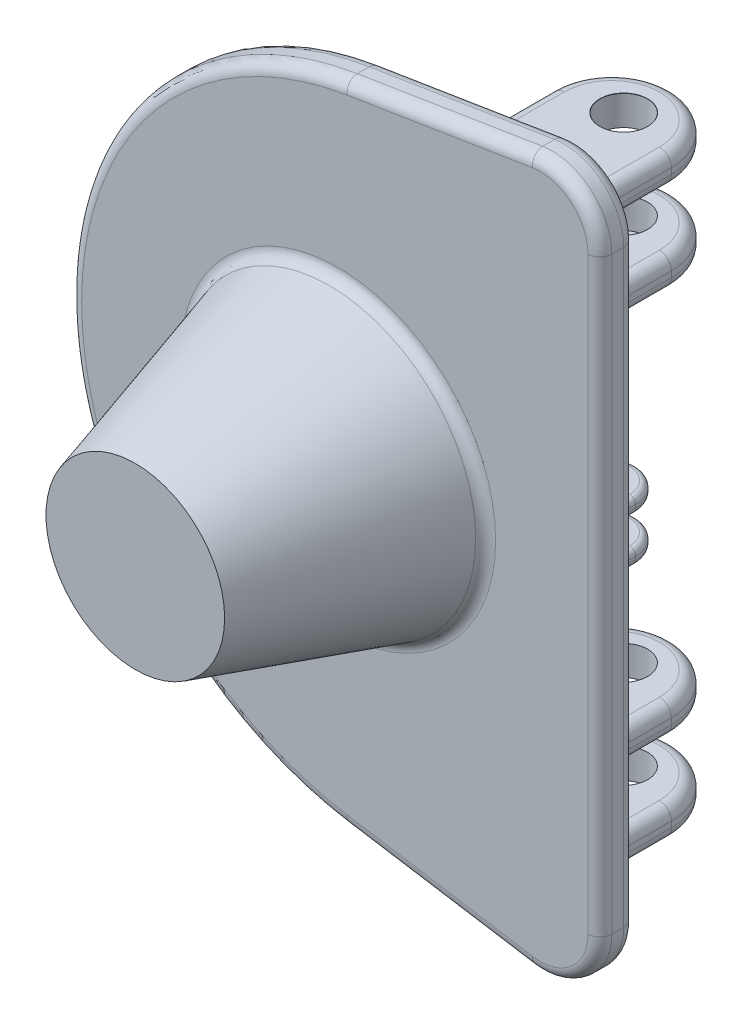
SolidWorks part; units mm, degrees
material "Maraging"
ref_plane "Front Plane" through (0, 0, 0) normal (0, 0, 1) x (1, 0, 0)
ref_plane "Top Plane" through (0, 0, 0) normal (0, 1, 0) x (1, 0, 0)
ref_plane "Right Plane" through (0, 0, 0) normal (1, 0, 0) x (0, 0, -1)
sketch "Sketch1" plane through (0, 0, 0) normal (0, 0, 1) x (1, 0, 0)
  line L0 (34, 49.4368) -> (34, -49.4368)
  line L3 (-8.7311, 54.3026) -> (22.4125, 59.31)
  line L4 (22.4125, -59.31) -> (-8.7311, -54.3026)
  circle A0 centre (0, 0) radius 60 construction
  arc A4 (-8.7311, 54.3026) -> (-8.7311, -54.3026) centre (0, 0) ccw
  arc A5 (34, -49.4368) -> (22.4125, -59.31) centre (24, -49.4368) cw
  arc A6 (34, 49.4368) -> (22.4125, 59.31) centre (24, 49.4368) ccw
  point P5 (34, -61.1731)
  point P13 (34, 61.1731)
  dimension "D1" = 120
  dimension "D2" = 55
  dimension "D3" = 34
  dimension "D4" = 10
extrude "Boss-Extrude1" add sketch "Sketch1" along normal blind 6
ref_plane "Plane1" through (-45, 0, 0) normal (1, 0, 0) x (0, 0, -1)
ref_plane "Plane2" through (5, 0, 0) normal (1, 0, 0) x (0, 0, -1)
sketch "Sketch9" plane through (-45, 0, 0) normal (1, 0, 0) x (0, 0, -1)
  line L0 (0, -10) -> (0, 10)
  line L3 (4, 3) -> (4, -3)
  line L4 (6, -5) -> (25, -5)
  line L5 (25, -10) -> (0, -10)
  line L6 (14.8178, 0) -> (-10.7829, 0) construction
  line L7 (25, 10) -> (0, 10)
  line L8 (6, 5) -> (25, 5)
  line L9 (25, -5) -> (25, -10)
  line L10 (25, 5) -> (25, 10)
  arc A2 (6, 5) -> (4, 3) centre (6, 3) ccw
  arc A3 (4, -3) -> (6, -5) centre (6, -3) ccw
  point P7 (12.5, -10)
  point P14 (4, 0)
  point P15 (0, 0)
  point P20 (4, 5)
  point P23 (4, -5)
  dimension "D5" = 2
  dimension "D2" = 4
  dimension "D4" = 5
  dimension "D1" = 25
  dimension "D3" = 5
extrude "Boss-Extrude3" add sketch "Sketch9" along normal blind 20
hole_wizard "Ø8.0mm Dowel Hole2" positions "3DSketch3" profile "Sketch10" hole size "Ø8.0" standard "ISO"
sketch3d "3DSketch3"
  line L0 (-25, 10, 0) -> (-45, 10, 0) construction
  point P0 (-35, 10, -17)
  point P6 (-35, 10, 0)
  dimension "D1" = 17
sketch "Sketch10" plane through (-35, 10, -17) normal (1, 0, 0) x (0, 0, 1)
  line L0 (0, 0) -> (0, 26.9034)
  line L1 (0, 26.9034) -> (4, 24.5)
  line L2 (4, 24.5) -> (4, 0.025)
  line L3 (4, 0.025) -> (4.025, 0)
  line L5 (4.025, 0) -> (0, 0)
  line L6 (-4, 0.025) -> (-4.025, 0) construction
  line L10 (0, 26.9034) -> (-4, 24.5) construction
  line L11 (0, -6.35) -> (0, 107.95) construction
  dimension "Hole Dia." = 8
  dimension "Hole Depth" = 24.5
  dimension "Near C'Sink Dia." = 8.05
  dimension "Near C'Sink Angle" = 90
  dimension "Drill Angle" = 118
sketch "Sketch11" plane through (0, 10, 0) normal (0, 1, 0) x (1, 0, 0)
  line L2 (-45, -18.15) -> (-45, 18.15) construction
  line L3 (-45, 15) -> (-45, 25)
  line L4 (-45, 25) -> (-25, 25)
  line L5 (-25, 25) -> (-25, 15)
  line L6 (-25, 25) -> (-25, 0) construction
  line L8 (-25, 25) -> (-45, 25) construction
  arc A0 (-45, 15) -> (-25, 15) centre (-35, 15) cw
  point P7 (-35, 25)
  line M6 (-45, 25) -> (-45, 0)
  line M8 (-25, 0) -> (-25, 25)
  line M9 (-25, 25) -> (-45, 25)
extrude "Cut-Extrude3" cut sketch "Sketch11" against normal blind 30 contours A0 L4 M6 | A0 M9 M8 region at (-27.2337, 10, -22.7663) region at (-42.7663, 10, -22.7663)
sketch "Sketch14" plane through (5, 0, 0) normal (1, 0, 0) x (0, 0, -1)
  line L0 (0, 40) -> (0, 30)
  line L2 (0, 30) -> (25, 30)
  line L3 (25, 30) -> (25, 35)
  line L4 (25, 35) -> (6, 35)
  line L5 (4, 37) -> (4, 43)
  line L6 (32.8816, 40) -> (-15.0482, 40) construction
  line L7 (25, 45) -> (6, 45)
  line L8 (25, 50) -> (25, 45)
  line L9 (0, 50) -> (25, 50)
  line L10 (0, 40) -> (0, 50)
  line L11 (0, -49.4368) -> (0, 49.4368) construction
  arc A0 (6, 35) -> (4, 37) centre (6, 37) cw
  arc A1 (6, 45) -> (4, 43) centre (6, 43) ccw
  point P14 (0, 35)
  point P17 (4, 40)
  point P22 (4, 35)
  point P25 (4, 45)
  dimension "D1" = 25
  dimension "D6" = 2
  dimension "D2" = 5
  dimension "D3" = 5
  dimension "D4" = 4
  dimension "D5" = 40
extrude "Boss-Extrude5" add sketch "Sketch14" along normal blind 20 contours L4 A0 L5 A1 L7 L8 L9 L10 L0 L2 L3
hole_wizard "Ø8.0mm Dowel Hole3" positions "3DSketch5" profile "Sketch17" hole size "Ø8.0" standard "ISO"
sketch3d "3DSketch5"
  line L0 (25, 50, 0) -> (5, 50, 0) construction
  point P0 (15, 50, -17)
  point P8 (15, 50, 0)
  dimension "D1" = 17
sketch "Sketch17" plane through (15, 50, -17) normal (1, 0, 0) x (0, 0, 1)
  line L0 (0, 0) -> (0, 26.9034)
  line L1 (0, 26.9034) -> (4, 24.5)
  line L2 (4, 24.5) -> (4, 0.025)
  line L3 (4, 0.025) -> (4.025, 0)
  line L5 (4.025, 0) -> (0, 0)
  line L6 (-4, 0.025) -> (-4.025, 0) construction
  line L10 (0, 26.9034) -> (-4, 24.5) construction
  line L11 (0, -6.35) -> (0, 107.95) construction
  dimension "Hole Dia." = 8
  dimension "Hole Depth" = 24.5
  dimension "Near C'Sink Dia." = 8.05
  dimension "Near C'Sink Angle" = 90
  dimension "Drill Angle" = 118
mirror "Mirror1" about plane through (0, 0, 0) normal (0, 1, 0) of "Ø8.0mm Dowel Hole3", "Boss-Extrude5"
sketch "Sketch19" plane through (0, 50, 0) normal (0, 1, 0) x (1, 0, 0)
  line L0 (5, 15) -> (5, 25)
  line L1 (5, 0) -> (5, 25) construction
  line L2 (5, 25) -> (25, 25)
  line L3 (25, 25) -> (25, 15)
  line L4 (25, 0) -> (25, 25) construction
  arc A0 (25, 15) -> (5, 15) centre (15, 15) ccw
  point P11 (15, 25)
  line M3 (5, 25) -> (5, 0)
  line M5 (25, 0) -> (25, 25)
  line M6 (25, 25) -> (5, 25)
extrude "Cut-Extrude4" cut sketch "Sketch19" against normal through all contours A0 L2 M3 | A0 M5 M6 region at (22.7663, 50, -22.7663) region at (7.2337, 50, -22.7663)
sketch "Sketch22" plane through (0, 0, 0) normal (1, 0, 0) x (0, 0, -1)
  line L15 (0, 27) -> (34, 27)
  line L17 (34, 27) -> (34, 24.5)
  line L18 (34, 24.5) -> (6, 24.5)
  line L19 (4, 22.5) -> (4, 21.5)
  line L20 (6, 19.5) -> (34, 19.5)
  line L21 (34, 19.5) -> (34, 17)
  line L22 (34, 17) -> (0, 17)
  line L23 (0, 17) -> (0, 27)
  line L24 (0, -49.4368) -> (0, 49.4368) construction
  arc A0 (4, 21.5) -> (6, 19.5) centre (6, 21.5) ccw
  arc A1 (6, 24.5) -> (4, 22.5) centre (6, 22.5) ccw
  point P4 (0, 22)
  point P13 (4, 19.5)
  point P16 (4, 24.5)
  dimension "D6" = 2
  dimension "D2" = 5
  dimension "D1" = 34
  dimension "D3" = 4
  dimension "D5" = 22
  dimension "D4" = 2.5
extrude "Boss-Extrude6" add sketch "Sketch22" against normal mid plane 10
hole_wizard "Ø5.0mm Dowel Hole1" positions "3DSketch6" profile "Sketch23" hole size "Ø5.0" standard "ISO"
sketch3d "3DSketch6"
  line L0 (-5, 17, 0) -> (5, 17, 0) construction
  point P0 (0, 17, -29)
  point P5 (0, 17, 0)
  dimension "D1" = 29
sketch "Sketch23" plane through (0, 17, -29) normal (1, 0, 0) x (0, 0, -1)
  line L0 (0, 0) -> (0, 26.0022)
  line L1 (0, 26.0022) -> (2.5, 24.5)
  line L2 (2.5, 24.5) -> (2.5, 0.025)
  line L3 (2.5, 0.025) -> (2.525, 0)
  line L5 (2.525, 0) -> (0, 0)
  line L6 (-2.5, 0.025) -> (-2.525, 0) construction
  line L10 (0, 26.0022) -> (-2.5, 24.5) construction
  line L11 (0, -6.35) -> (0, 107.95) construction
  dimension "Hole Dia." = 5
  dimension "Hole Depth" = 24.5
  dimension "Near C'Sink Dia." = 5.05
  dimension "Near C'Sink Angle" = 90
  dimension "Drill Angle" = 118
mirror "Mirror2" about plane through (0, 0, 0) normal (0, 1, 0) of "Ø5.0mm Dowel Hole1", "Boss-Extrude6"
sketch "Sketch25" plane through (0, 27, 0) normal (0, 1, 0) x (1, 0, 0)
  line L0 (-5, 29) -> (-5, 34)
  line L1 (-5, 34) -> (-5, 0) construction
  line L2 (-5, 34) -> (5, 34)
  line L3 (5, 34) -> (5, 0) construction
  line L4 (-5, 34) -> (5, 34) construction
  line L5 (5, 34) -> (5, 29)
  arc A0 (5, 29) -> (-5, 29) centre (0, 29) ccw
  line M3 (5, 0) -> (5, 34)
  line M4 (5, 34) -> (-5, 34)
  line M5 (-5, 34) -> (-5, 0)
extrude "Cut-Extrude6" cut sketch "Sketch25" against normal through all contours A0 L2 M5 | A0 M3 M4 region at (3.8832, 27, -32.8832) region at (-3.8832, 27, -32.8832)
ref_plane "Plane3" through (0, 0, 40) normal (0, 0, 1) x (1, 0, 0)
sketch "Sketch26" plane through (0, 0, 40) normal (0, 0, 1) x (1, 0, 0)
  circle A0 centre (-10, 0) radius 15
  dimension "D1" = 30
  dimension "D2" = 10
sketch "Sketch27" plane through (0, 0, 6) normal (0, 0, 1) x (1, 0, 0)
  circle A2 centre (-10, 0) radius 25
  dimension "D1" = 50
  dimension "D2" = 10
loft "Loft1" add profiles "Sketch27", "Sketch26" connector at (-30.677, 14.0521, 6) connector at (-22.5835, 8.1643, 40)
fillet "Fillet4" radius 2 12 edges at (6.8407, 56.8063, 6) (30.4856, 57.0485, 6) (34, 0, 6) (30.4856, -57.0485, 6) (6.8407, -56.8063, 6) (6.8407, 56.8063, 0) (30.4856, 57.0485, 0) (34, 0, 0) (30.4856, -57.0485, 0) (6.8407, -56.8063, 0) (-55, 0, 6) (-55, 0, 0)
fillet "Fillet5" radius 2 66 edges at (25, 50, -7.5) (15, 50, -25) (15, 35, -25) (25, 35, -10.5) (25, 35.5858, -4.5858) (25, 40, -4) (25, 44.4142, -4.5858) (25, 45, -10.5) (15, 45, -25) (5, 45, -10.5) (5, 44.4142, -4.5858) (5, 40, -4) (5, 35.5858, -4.5858) (25, 30, -7.5) (15, 30, -25) (25, -30, -7.5) (15, -30, -25) (15, -45, -25) (25, -45, -10.5) (25, -44.4142, -4.5858) (25, -40, -4) (25, -35.5858, -4.5858) (25, -35, -10.5) (15, -35, -25) (5, -35, -10.5) (5, -35.5858, -4.5858) (5, -40, -4) (5, -44.4142, -4.5858) (25, -50, -7.5) (15, -50, -25) (-25, 10, -7.5) (-35, 10, -25) (-35, -5, -25) (-25, -5, -10.5) (-25, -4.4142, -4.5858) (-25, 0, -4) (-25, 4.4142, -4.5858) (-25, 5, -10.5) (-35, 5, -25) (-45, 5, -10.5) (-45, 4.4142, -4.5858) (-45, 0, -4) (-45, -4.4142, -4.5858) (-25, -10, -7.5) (-35, -10, -25) (5, 50, -7.5) (5, 35, -10.5) (5, 30, -7.5) (5, -30, -7.5) (5, -45, -10.5) (5, -50, -7.5) (-45, 10, -7.5) (-45, -5, -10.5) (-45, -10, -7.5) (-45, 0, 0) (5, 40, 0) (25, -40, 0) (-35, 10, 0) (-35, -10, 0) (15, 30, 0) (15, 50, 0) (15, -30, 0) (15, -50, 0) (25, 40, 0) (-25, 0, 0) (5, -40, 0)
fillet "Fillet6" radius 1 40 edges at (5, -19.5, -17.5) (0, -19.5, -34) (-5, -19.5, -17.5) (-5, -22, -4) (-5, -23.9142, -4.5858) (-5, -24.5, -17.5) (0, -24.5, -34) (5, -24.5, -17.5) (5, -23.9142, -4.5858) (5, -22, -4) (-5, 17, -14.5) (0, 17, -34) (5, 27, -14.5) (0, 27, -34) (-5, 23.9142, -4.5858) (-5, 22, -4) (-5, 20.0858, -4.5858) (-5, 19.5, -17.5) (0, 19.5, -34) (5, 19.5, -17.5) (5, 20.0858, -4.5858) (5, 22, -4) (5, 23.9142, -4.5858) (5, 24.5, -17.5) (0, 24.5, -34) (5, -17, -14.5) (0, -17, -34) (5, -27, -14.5) (0, -27, -34) (5, -22, 0) (0, -27, 0) (-5, -22, 0) (0, -17, 0) (-5, -20.0858, -4.5858) (5, -20.0858, -4.5858) (5, 17, -14.5) (-5, 27, -14.5) (-5, 24.5, -17.5) (-5, -17, -14.5) (-5, -27, -14.5)
fillet "Fillet7" radius 2 1 edges at (15, 0, 6)
equation "\"altura\"= 25"
equation "\"D1@Sketch9\"=\"altura\""
equation "\"largura\"= 5"
equation "\"D3@Sketch9\"=\"largura\""
equation "\"espacamento\"=5"
equation "\"D4@Sketch9\"=\"espacamento\""
equation "\"alt_base\"= 4"
equation "\"D2@Sketch9\"=\"alt_base\""
equation "\"raio_int\"= 2"
equation "\"ra\"=2"
equation "\"D5@Sketch9\"=\"ra\""
equation "\"D1@Sketch14\"=\"altura\""
equation "\"D2@Sketch14\"=\"largura\""
equation "\"D3@Sketch14\"=\"espacamento\""
equation "\"D6@Sketch14\"=\"raio_int\""
equation "\"alt_furo\"= 17"
equation "\"D1@3DSketch3\"=\"alt_furo\""
equation "\"D1@3DSketch5\"=\"alt_furo\""
equation "\"D1@Sketch22\"=\"altura\"+9"
equation "\"D2@Sketch22\"=\"espacamento\""
equation "\"D3@Sketch22\"=\"alt_base\""
equation "\"D6@Sketch22\"=\"raio_int\""
equation "\"D1@3DSketch6\"=\"alt_furo\"+12"
equation "\"D4@Sketch22\"=\"largura\"/2"
